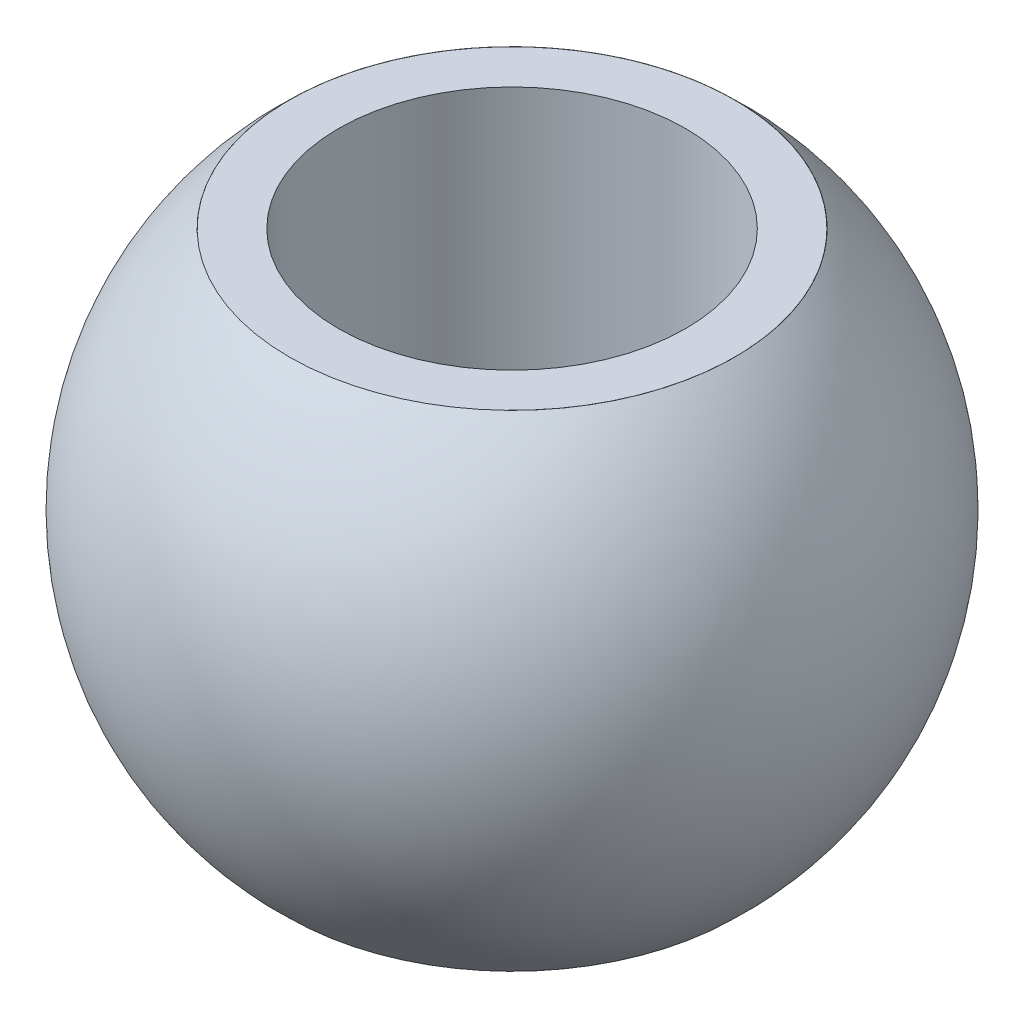
SolidWorks part; units mm, degrees
ref_plane "Front Plane" through (0, 0, 0) normal (0, 0, 1) x (1, 0, 0)
ref_plane "Top Plane" through (0, 0, 0) normal (0, 1, 0) x (1, 0, 0)
ref_plane "Right Plane" through (0, 0, 0) normal (1, 0, 0) x (0, 0, -1)
sketch "Sketch1" plane through (0, 0, 0) normal (0, 1, 0) x (1, 0, 0)
  line L0 (-9.5, 0) -> (9.5, 0) construction
  circle A0 centre (0, 0) radius 5
  circle A1 centre (0, 0) radius 6.42
  circle A2 centre (0, 0) radius 9.5
  dimension "D1" = 10
  dimension "D2" = 12.84
  dimension "D3" = 19
revolve "Revolve1" add sketch "Sketch1" angle 360 about L0 region at (0, 0, -5.1436) region at (0, 0, -2.1221) region at (0, 0, -6.6324)
extrude "Cut-Extrude1" cut sketch "Sketch1<3>" against normal through all and the other way through all contours A0 L0 | L0 A0 region at (0, 0, 2.1221) region at (0, 0, -2.1221)
sketch "Sketch1<3>" plane through (0, 0, 0) normal (0, 1, 0) x (1, 0, 0) same geometry as "Sketch1"
extrude "Cut-Extrude2" cut sketch "Sketch1<4>" along normal through all from offset 7 contours L0 A1 A0 | A1 L0 A0 region at (0, 0, -5.1436) region at (5.71, 0, 0.1436)
sketch "Sketch1<4>" plane through (0, 0, 0) normal (0, 1, 0) x (1, 0, 0) same geometry as "Sketch1"
extrude "Cut-Extrude3" cut sketch "Sketch1<5>" against normal through all from offset 7 contours A1 L0 A0 | L0 A1 A0 region at (0, 0, -5.1436) region at (5.71, 0, 0.1436) offset against normal yes
sketch "Sketch1<5>" plane through (0, 0, 0) normal (0, 1, 0) x (1, 0, 0) same geometry as "Sketch1"
